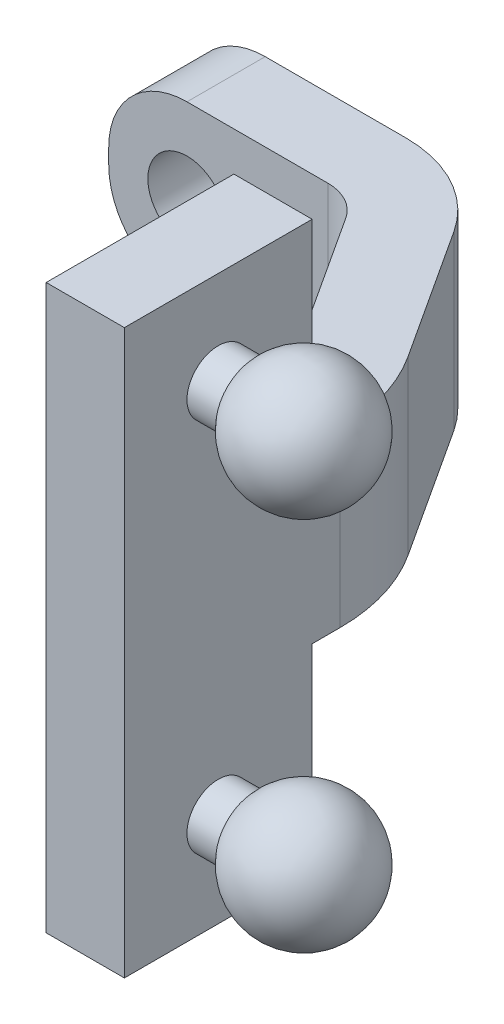
SolidWorks part; units mm, degrees
ref_plane "前视基准面" through (0, 0, 0) normal (0, 0, 1) x (1, 0, 0)
ref_plane "上视基准面" through (0, 0, 0) normal (0, 1, 0) x (1, 0, 0)
ref_plane "右视基准面" through (0, 0, 0) normal (1, 0, 0) x (0, 0, -1)
other "Configuration Table"
sketch "草图1" plane through (0, 0, 0) normal (0, 1, 0) x (1, 0, 0)
  line L0 (0, 0) -> (7, 0)
  line L1 (14, -9.1042) -> (14, -16)
  line L2 (0, -2.5) -> (7, -2.5)
  line L3 (11.5, -9.1042) -> (11.5, -16)
  line L4 (11.5, -16) -> (14, -16)
  line L5 (0, 0) -> (0, -2.5)
  line L6 (10.3535, -1.8196) -> (13.0862, -6.0224)
  line L7 (8.2575, -3.1823) -> (10.9903, -7.3852)
  arc A0 (7, 0) -> (10.3535, -1.8196) centre (7, -4) cw
  arc A3 (7, -2.5) -> (8.2575, -3.1823) centre (7, -4) cw
  arc A6 (9.6623, -0.4928) -> (14, -9.1042) centre (3.2834, -9.1042) cw construction
  arc A7 (10.3535, -1.8196) -> (9.6623, -0.4928) centre (16.8788, 2.4233) ccw construction
  arc A8 (8.2575, -3.1823) -> (7.6722, -2.1578) centre (16.8788, 2.4233) ccw construction
  arc A9 (7.6722, -2.1578) -> (11.5, -9.1042) centre (3.2834, -9.1042) cw construction
  arc A10 (13.0862, -6.0224) -> (14, -9.1042) centre (8.3466, -9.1042) cw
  arc A11 (11.5, -9.1042) -> (10.9903, -7.3852) centre (8.3466, -9.1042) ccw
  dimension "D1" = 2.5
  dimension "D3" = 4
  dimension "D4" = 14
  dimension "D2" = 7
  dimension "D6" = 16
extrude "凸台-拉伸1" add sketch "草图1" along normal mid plane 5.5
sketch "草图2" plane through (0, 0, 0) normal (0, 0, -1) x (-1, 0, 0)
  line L0 (0, 2.75) -> (0, -2.75) construction
  circle A0 centre (-2.5, 0) radius 1.25
  point P5 (0, 0)
  dimension "D1" = 2.5
  dimension "D2" = 2.5
extrude "切除-拉伸1" cut sketch "草图2" against normal blind 10
fillet "圆角2" radius 2.5 2 edges at (0, -2.75, 1.25) (0, 2.75, 1.25)
sketch "草图4" plane through (11.5, 0, 0) normal (-1, 0, 0) x (0, 0, 1)
  line L0 (16, 2.75) -> (16, -2.75) construction
  line L1 (10, 9) -> (16, 9)
  line L2 (10, 9) -> (10, -9)
  line L3 (10, -9) -> (16, -9)
  line L4 (16, 9) -> (16, -9)
  line L5 (10, 9) -> (16, -9) construction
  line L6 (10, -9) -> (16, 9) construction
  point P0 (13, 0)
  dimension "D1" = 18
  dimension "D2" = 6
extrude "凸台-拉伸2" add sketch "草图4" against normal up to surface (2.5 mm away) up to face at (14, 0, 12.5521)
sketch "草图5" plane through (14, 0, 0) normal (1, 0, 0) x (0, 0, -1)
  line L0 (-10, 9) -> (-16, 9) construction
  line L1 (-10, 2.75) -> (-10, 9) construction
  circle A0 centre (-13, 6) radius 1
  point P6 (-15.4229, 6.9817)
  dimension "D1" = 2
  dimension "D2" = 3
  dimension "D3" = 3
extrude "凸台-拉伸3" add sketch "草图5" along normal blind 1
ref_axis "基准轴1" through (15, 6, 13) along (-1, 0, 0)
ref_plane "基准面1" through (0, 0, 13) normal (0, 0, -1) x (-1, 0, 0)
sketch "草图6" plane through (0, 0, 13) normal (0, 0, -1) x (-1, 0, 0)
  line L0 (-15, 6) -> (-18.7321, 6)
  line L1 (-15, 7) -> (-15, 5) construction
  line L2 (-15, 6) -> (-14, 6) construction
  line L3 (-15, 6) -> (-15, 7)
  line L4 (-14, 7) -> (-15, 7) construction
  arc A0 (-15, 7) -> (-18.7321, 6) centre (-16.7321, 6) ccw
  dimension "D1" = 4
revolve "旋转1" add sketch "草图6" angle 360 about L0
mirror "镜向1" about plane through (0, 0, 0) normal (0, 1, 0) of "凸台-拉伸3", "旋转1"
